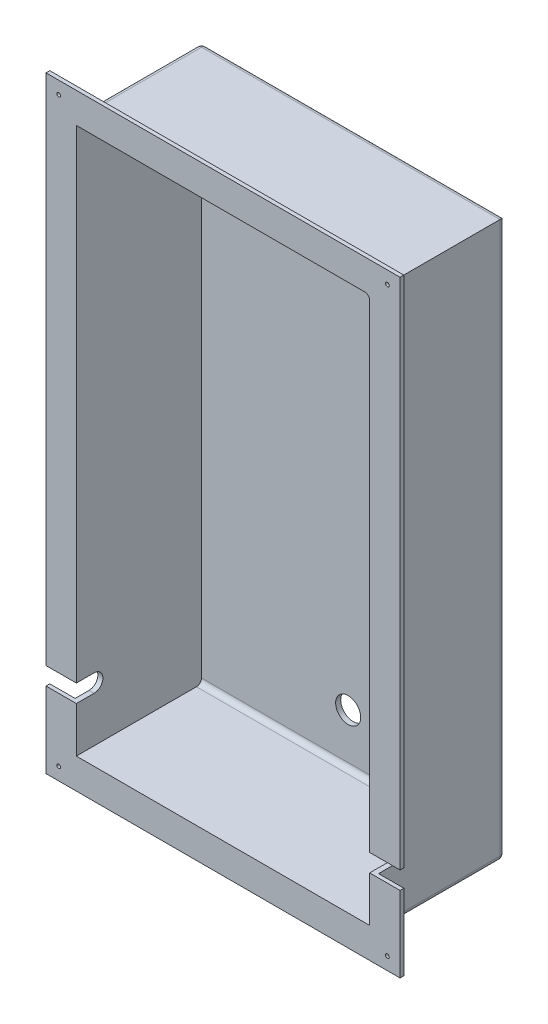
SolidWorks part; units mm, degrees
ref_plane "Front Plane" through (0, 0, 0) normal (0, 0, 1) x (1, 0, 0)
ref_plane "Top Plane" through (0, 0, 0) normal (0, 1, 0) x (1, 0, 0)
ref_plane "Right Plane" through (0, 0, 0) normal (1, 0, 0) x (0, 0, -1)
sketch "Sketch1" plane through (0, 0, 0) normal (0, 0, 1) x (1, 0, 0)
  line L1 (-60, 110) -> (60, 110)
  line L2 (-60, 110) -> (-60, -110)
  line L3 (-60, -110) -> (60, -110)
  line L4 (60, 110) -> (60, -110)
  line L5 (-60, 110) -> (60, -110) construction
  line L6 (-60, -110) -> (60, 110) construction
  point P0 (0, 0)
  dimension "D1" = 120
  dimension "D2" = 220
extrude "Boss-Extrude1" add sketch "Sketch1" along normal blind 50
sketch "Sketch2" plane through (0, 0, 50) normal (0, 0, 1) x (1, 0, 0)
  line L1 (-70, 120) -> (70, 120)
  line L2 (-70, 120) -> (-70, -120)
  line L3 (-70, -120) -> (70, -120)
  line L4 (70, 120) -> (70, -120)
  line L5 (60, 110) -> (-60, 110) construction
  line L6 (-60, 110) -> (-60, -110) construction
  line L7 (60, -110) -> (60, 110) construction
  line L8 (-60, -110) -> (60, -110) construction
  dimension "D1" = 10
  dimension "D2" = 10
  dimension "D3" = 10
  dimension "D4" = 10
extrude "Boss-Extrude2" add sketch "Sketch2" along normal blind 1.5 contours L2 L1 L4 L3
shell "Shell1" thickness 2 removed face at (0, 0, 51.5)
hole_wizard "Ø3.0mm Dowel Hole2" [suppressed] positions "Sketch5" profile "Sketch6" hole size "Ø3.0" standard "ANSI Metric"
sketch "Sketch5" plane through (-291.7811, -234.7839, 0) normal (0, 0, -1) x (-1, 0, 0)
  point P0 (-307.4711, 251.9022)
  point P1 (-277.4711, 251.9022)
  point P2 (-277.4711, 217.6656)
  point P3 (-307.4711, 217.6656)
sketch "Sketch6" plane through (15.69, 17.1183, 0) normal (1, 0, 0) x (0, 1, 0)
  line L0 (0, 0) -> (0, 38.499)
  line L1 (0, 38.499) -> (1.5, 38.499)
  line L2 (1.5, 38.499) -> (1.5, 0)
  line L3 (1.5, 0) -> (0, 0)
  line L4 (0, -6.35) -> (0, 107.95) construction
  dimension "Thru Hole Dia." = 3
  dimension "Thru Hole Depth" = 38.499
sketch "Sketch8" plane through (58, 0, 0) normal (-1, 0, 0) x (0, 0, 1)
  line L0 (51.5, -83) -> (44.5, -83)
  line L1 (51.5, -83) -> (51.5, -90)
  line L2 (51.5, -90) -> (44.5, -90)
  line L4 (51.5, 120) -> (51.5, -120) construction
  line L5 (50, -110) -> (0, -110) construction
  arc A0 (44.5, -90) -> (44.5, -83) centre (44.5, -86.5) cw
  dimension "D1" = 7
  dimension "D2" = 7
  dimension "D3" = 20
extrude "Cut-Extrude1" cut sketch "Sketch8" against normal through all both and the other way through all
fillet "Fillet1" radius 2 4 edges at (0, -108, 2) (-60, 0, 0) (0, 110, 0) (60, 0, 0)
fillet "Fillet2" radius 2 8 edges at (60, -110, 26) (59.4142, -110, 0.5858) (0, -110, 0) (-59.4142, -110, 0.5858) (-59.4142, 109.4142, 0.5858) (-60, -110, 26) (-60, 110, 26) (58, 108, 26.75)
sketch "Sketch9" plane through (0, 0, 0) normal (0, 0, -1) x (-1, 0, 0)
  line L0 (-58, -108) -> (58, -108) construction
  circle A0 centre (0, -88) radius 4.9511
  point P5 (0, -108)
  dimension "D1" = 9.9022
  dimension "D2" = 20
extrude "Cut-Extrude2" cut sketch "Sketch9" against normal through all
hole_wizard "Ø1.5mm Dowel Hole1" positions "Sketch10" profile "Sketch11" hole size "Ø1.5" standard "ANSI Metric" end condition through all
sketch "Sketch10" plane through (-164.6271, -264.1252, 50) normal (0, 0, -1) x (-1, 0, 0)
  point P0 (-229.6271, 379.1252)
  point P1 (-99.6271, 379.1252)
  point P2 (-229.6271, 149.1252)
  point P3 (-99.6271, 149.1252)
sketch "Sketch11" plane through (65, 115, 50) normal (1, 0, 0) x (0, 1, 0)
  line L0 (0, 0) -> (0, 1.5)
  line L1 (0, 1.5) -> (0.75, 1.5)
  line L2 (0.75, 1.5) -> (0.75, 0)
  line L5 (0.75, 0) -> (0, 0)
  line L11 (0, -6.35) -> (0, 107.95) construction
  dimension "Thru Hole Dia." = 1.5
  dimension "Thru Hole Depth" = 1.5
equation "\"dist_to_lock\"= 1cm"
equation "\"door_depth\"= 4.7cm"
equation "\"D2@Sketch2\"=\"D1@Sketch2\""
equation "\"D3@Sketch2\"=\"D1@Sketch2\""
